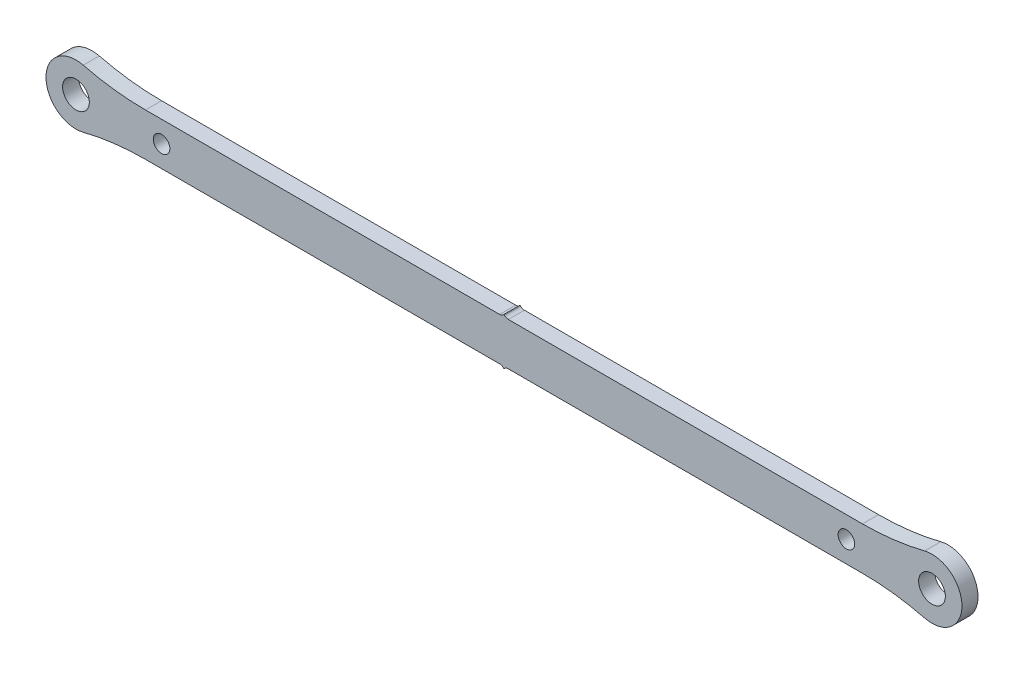
SolidWorks part; units mm, degrees
ref_plane "Front Plane" through (0, 0, 0) normal (0, 0, 1) x (1, 0, 0)
ref_plane "Top Plane" through (0, 0, 0) normal (0, 1, 0) x (1, 0, 0)
ref_plane "Right Plane" through (0, 0, 0) normal (1, 0, 0) x (0, 0, -1)
sketch "Sketch1" plane through (0, 0, 0) normal (0, 0, 1) x (1, 0, 0)
  line L0 (-80, 0) -> (80, 0) construction
  line L1 (-76.0808, -4) -> (76.0808, -4)
  line L3 (-76.0808, 4) -> (76.0808, 4)
  line L5 (-76.0808, -4) -> (76.0808, 4) construction
  line L6 (-76.0808, 4) -> (76.0808, -4) construction
  circle A0 centre (-80, 0) radius 1.5
  arc A1 (-76.0808, 4) -> (-76.0808, -4) centre (-80, 0) ccw
  circle A2 centre (80, 0) radius 1.5
  arc A3 (76.0808, -4) -> (76.0808, 4) centre (80, 0) ccw
  circle A4 centre (-64, 0) radius 1.55
  circle A5 centre (64, 0) radius 1.55
  point P0 (0, 0)
  point P6 (-80, 0)
  point P7 (80, 0)
  dimension "D3" = 3
  dimension "D2" = 5.6
  dimension "D5" = 3.1
  dimension "D1" = 160
  dimension "D4" = 8
  dimension "D6" = 16
  dimension "D7" = 16
extrude "Boss-Extrude1" add sketch "Sketch1" along normal blind 3
ref_axis "Axis2" through (80, 0, 0) along (0, 0, 1)
ref_axis "Axis3" through (-80, 0, 0) along (0, 0, 1)
sketch "Sketch3" plane through (0, 0, 0) normal (0, 1, 0) x (1, 0, 0)
  line L0 (76.0808, 0) -> (-76.0808, 0) construction
  line L1 (80, 0) -> (80, -3) construction
  line L2 (76.0808, -3) -> (85.6, -3) construction
  line L3 (-80, 0) -> (-80, -3) construction
  line L4 (80.5, 0) -> (82.4981, 0)
  line L5 (80.5, 0) -> (80.5, -3)
  line L6 (80.5, -3) -> (82.4981, -3)
  line L7 (82.4981, 0) -> (82.4981, -3)
  line L8 (82.5981, 0) -> (82.5981, -3) construction
  line L9 (85.6, 0) -> (76.0808, 0) construction
  line L10 (0, 0) -> (0, -3) construction
  line L11 (76.0808, -3) -> (-76.0808, -3) construction
  circle A0 centre (80, 1.5) radius 3 construction
  circle A1 centre (-80, 1.5) radius 3 construction
  dimension "D1" = 6
  dimension "D2" = 1.5
  dimension "D3" = 0.1
  dimension "D4" = 0.5
ref_point "Point1"
ref_point "Point2"
revolve "Cut-Revolve1" cut sketch "Sketch3" angle 360 about axis through (80, 0, 0) along (0, 0, 1)
mirror "Mirror1" about plane through (0, 0, 0) normal (1, 0, 0) of "Cut-Revolve1"
fillet "Fillet1" radius 48 4 edges at (76.0808, -4, 1.5) (76.0808, 4, 1.5) (-76.0808, -4, 1.5) (-76.0808, 4, 1.5)
sketch "Sketch4" plane through (0, 0, 3) normal (0, 0, 1) x (1, 0, 0)
  line L0 (0, -4.4) -> (0.1071, -4.2929)
  line L1 (0, -4.4) -> (-0.1071, -4.2929)
  line L2 (0.1071, 4.2929) -> (0, 4.4)
  line L3 (-0.1071, 4.2929) -> (0, 4.4)
  line L4 (0, -4.4) -> (0, 4.4) construction
  line L5 (4.4, 0) -> (-4.4, 0) construction
  line L6 (67.0015, 4) -> (-67.0015, 4) construction
  line L7 (-4.4, 4) -> (-4.4, -4)
  line L8 (-67.0015, -4) -> (67.0015, -4) construction
  line L9 (-4.4, -4) -> (-0.8142, -4)
  line L10 (4.4, -4) -> (4.4, 4)
  line L11 (4.4, 4) -> (0.8142, 4)
  line L12 (-0.8142, 4) -> (-4.4, 4)
  line L13 (0.8142, -4) -> (4.4, -4)
  arc A0 (-0.8142, -4) -> (-0.1071, -4.2929) centre (-0.8142, -5) cw
  arc A1 (0.8142, -4) -> (0.1071, -4.2929) centre (0.8142, -5) ccw
  arc A2 (0.8142, 4) -> (0.1071, 4.2929) centre (0.8142, 5) cw
  arc A3 (-0.1071, 4.2929) -> (-0.8142, 4) centre (-0.8142, 5) cw
  point P1 (0, 0)
  dimension "D2" = 1
  dimension "D1" = 0.4
extrude "Boss-Extrude3" add sketch "Sketch4" against normal through all
equation "\"D7@Sketch1\"=\"D6@Sketch1\""
